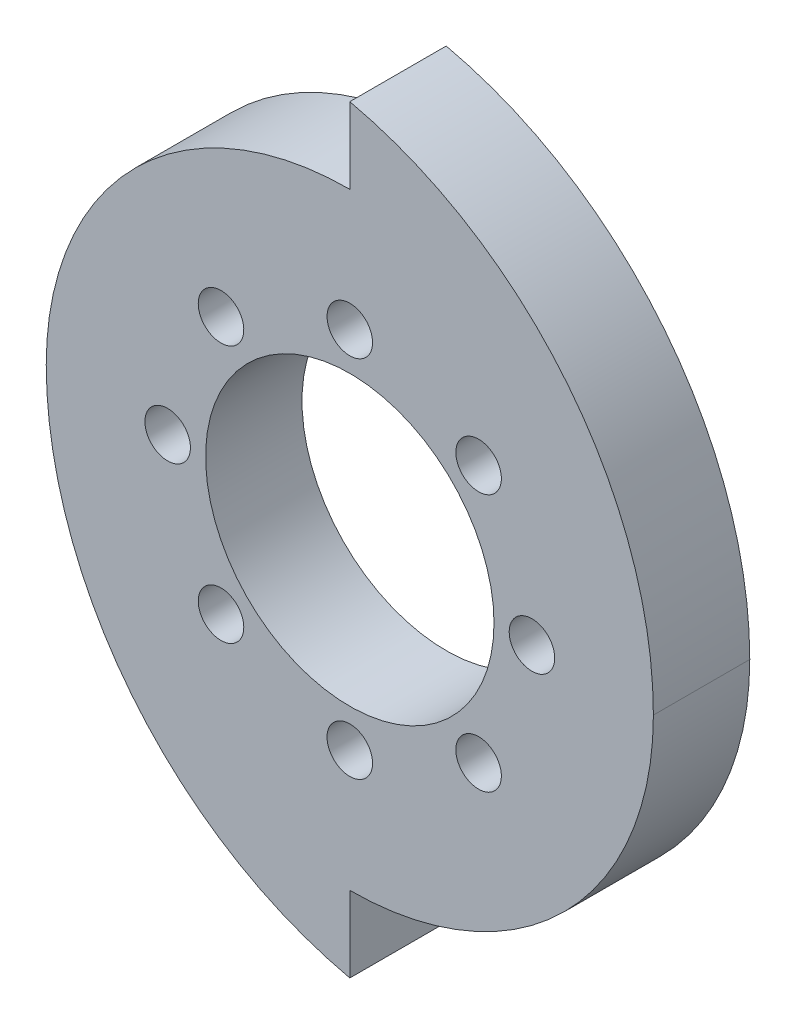
SolidWorks part; units mm, degrees
material "AISI 316 Stainless Steel Sheet (SS)"
ref_plane "Front Plane" through (0, 0, 0) normal (0, 0, 1) x (1, 0, 0)
ref_plane "Top Plane" through (0, 0, 0) normal (0, 1, 0) x (1, 0, 0)
ref_plane "Right Plane" through (0, 0, 0) normal (1, 0, 0) x (0, 0, -1)
sketch "Sketch3" plane through (0, 0, 0) normal (0, 0, 1) x (1, 0, 0)
  line L5 (0, 20) -> (0, 25)
  line L12 (0, -20) -> (0, -25)
  arc A9 (0, 25) -> (-20, 0) centre (5.625, 0) ccw construction
  arc A11 (0, -25) -> (20, 0) centre (-5.625, 0) ccw construction
  arc A14 (0, 25) -> (20, 0) centre (-5.625, 0) cw
  arc A15 (0, -25) -> (-20, 0) centre (5.625, 0) cw
  arc A16 (0, 20) -> (-20, 0) centre (0, 0) ccw
  arc A17 (20, 0) -> (0, -20) centre (0, 0) cw
  dimension "D2" = 5
  dimension "D1" = 40
extrude "Boss-Extrude1" add sketch "Sketch3" along normal blind 6.35
sketch "Sketch4" plane through (0, 0, 6.35) normal (0, 0, 1) x (1, 0, 0)
  circle A10 centre (0, 0) radius 9.5
  circle A11 centre (0, 12) radius 1.5
  dimension "D2" = 12
  dimension "D3" = 19
  dimension "D1" = 3
extrude "Cut-Extrude1" cut sketch "Sketch4" against normal through all
ref_axis "Axis1" through (0, 0, -0.475) along (0, 0, 1)
pattern_circular "CirPattern1" count 8 over 360 about axis through (0, 0, -0.475) along (0, 0, 1) of "Cut-Extrude1"
